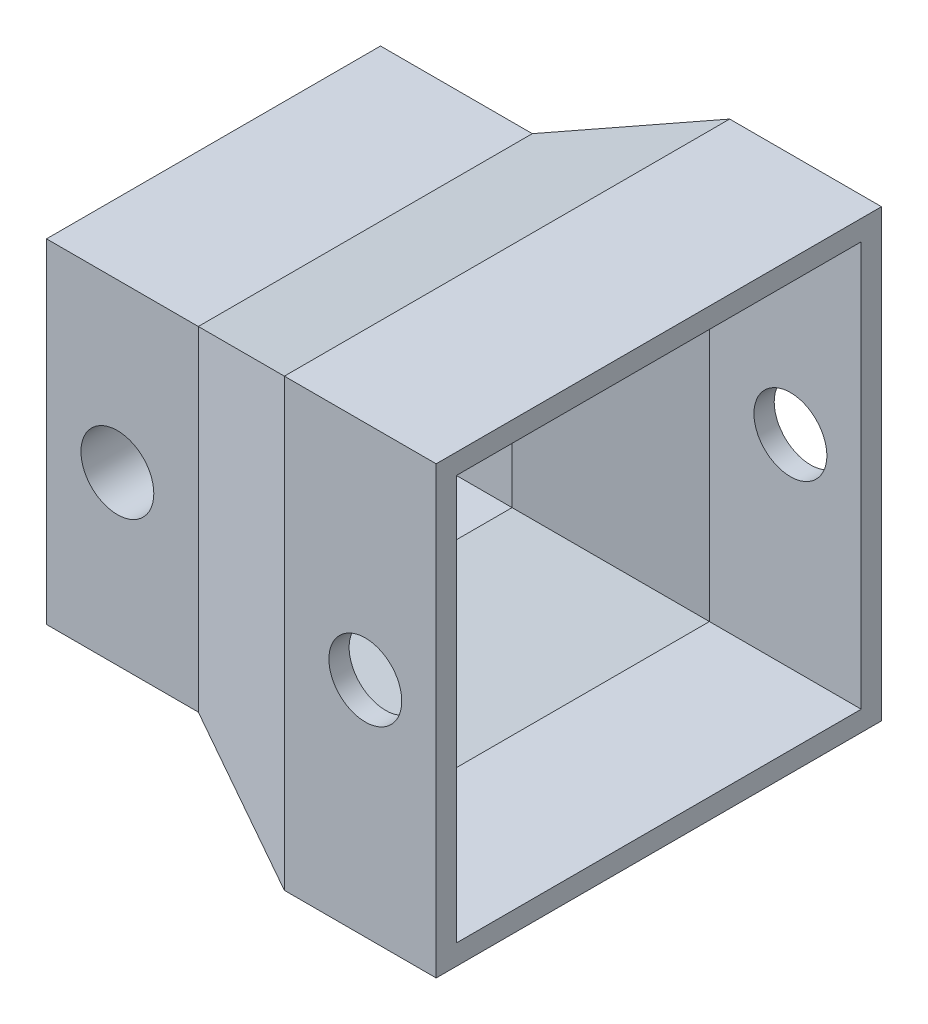
SolidWorks part; units mm, degrees
ref_plane "正面" through (0, 0, 0) normal (0, 0, 1) x (1, 0, 0)
ref_plane "平面" through (0, 0, 0) normal (0, 1, 0) x (1, 0, 0)
ref_plane "右側面" through (0, 0, 0) normal (1, 0, 0) x (0, 0, -1)
sketch "ｽｹｯﾁ1" plane through (0, 0, 0) normal (0, 0, 1) x (1, 0, 0)
  circle A0 centre (0, 0) radius 2.5
  dimension "D1" = 5
extrude "ﾎﾞｽ - 押し出し1" add sketch "ｽｹｯﾁ1" along normal blind 1.5
sketch "ｽｹｯﾁ2" plane through (0, 0, 1.5) normal (0, 0, 1) x (1, 0, 0)
  circle A0 centre (0, 0) radius 3.5
  dimension "D1" = 7
extrude "ﾎﾞｽ - 押し出し2" add sketch "ｽｹｯﾁ2" along normal blind 1
sketch "ｽｹｯﾁ3" plane through (0, 0, 2.5) normal (0, 0, 1) x (1, 0, 0)
  circle A0 centre (0, 0) radius 2.5 construction
  circle A1 centre (0, 0) radius 2.5
extrude "ﾎﾞｽ - 押し出し3" add sketch "ｽｹｯﾁ3" along normal blind 2.5
sketch "ｽｹｯﾁ4" plane through (0, 0, 5) normal (0, 0, 1) x (1, 0, 0)
  circle A1 centre (0, 0) radius 3.5
  circle A2 centre (0, 0) radius 3.5
  dimension "D1" = 0
extrude "ﾎﾞｽ - 押し出し4" add sketch "ｽｹｯﾁ4" along normal blind 1
sketch "ｽｹｯﾁ5" plane through (0, 0, 6) normal (0, 0, 1) x (1, 0, 0)
  circle A0 centre (0, 0) radius 2.5 construction
  circle A1 centre (0, 0) radius 2.5
extrude "ﾎﾞｽ - 押し出し5" add sketch "ｽｹｯﾁ5" along normal blind 2.5
sketch "ｽｹｯﾁ6" plane through (0, 0, 8.5) normal (0, 0, 1) x (1, 0, 0)
  circle A1 centre (0, 0) radius 3.5
  circle A2 centre (0, 0) radius 3.5
  dimension "D1" = 0
extrude "ﾎﾞｽ - 押し出し6" add sketch "ｽｹｯﾁ6" along normal blind 1
sketch "ｽｹｯﾁ7" plane through (0, 0, 9.5) normal (0, 0, 1) x (1, 0, 0)
  circle A0 centre (0, 0) radius 2.5 construction
  circle A1 centre (0, 0) radius 2.5
extrude "ﾎﾞｽ - 押し出し7" add sketch "ｽｹｯﾁ7" along normal blind 2.5
sketch "ｽｹｯﾁ10" plane through (0, 0, 12) normal (0, 0, 1) x (1, 0, 0)
  circle A1 centre (0, 0) radius 3.5
  circle A2 centre (0, 0) radius 3.5
  dimension "D1" = 0
extrude "ﾎﾞｽ - 押し出し9" add sketch "ｽｹｯﾁ10" along normal blind 1
sketch "ｽｹｯﾁ11" plane through (0, 0, 13) normal (0, 0, 1) x (1, 0, 0)
  circle A0 centre (0, 0) radius 2.5 construction
  circle A1 centre (0, 0) radius 2.5
extrude "ﾎﾞｽ - 押し出し10" add sketch "ｽｹｯﾁ11" along normal blind 1.5
sketch "ｽｹｯﾁ12" plane through (0, 0, 14.5) normal (0, 0, 1) x (1, 0, 0)
  circle A0 centre (0, 0) radius 1.8
  dimension "D1" = 3.6
extrude "ｶｯﾄ - 押し出し2" cut sketch "ｽｹｯﾁ12" against normal through all
ref_plane "平面1" through (15, 0, 0) normal (1, 0, 0) x (0, 0, -1)
sketch "ｽｹｯﾁ13" plane through (15, 0, 0) normal (1, 0, 0) x (0, 0, -1)
  line L0 (0, 0) -> (-7.25, 0) construction
  line L1 (-18.25, -11) -> (3.75, -11)
  line L2 (-18.25, -11) -> (-18.25, 11)
  line L3 (-18.25, 11) -> (3.75, 11)
  line L4 (3.75, -11) -> (3.75, 11)
  line L5 (-18.25, -11) -> (3.75, 11) construction
  line L6 (-18.25, 11) -> (3.75, -11) construction
  line L7 (-7.25, 0) -> (-14.5, 0) construction
  line L8 (-14.5, 2.5) -> (-14.5, -2.5) construction
  line L10 (2.75, -10) -> (-17.25, -10)
  line L11 (2.75, -10) -> (2.75, 10)
  line L12 (2.75, 10) -> (-17.25, 10)
  line L13 (-17.25, -10) -> (-17.25, 10)
  line L14 (2.75, -10) -> (-17.25, 10) construction
  line L15 (2.75, 10) -> (-17.25, -10) construction
  point P4 (-7.25, 0)
  dimension "D1" = 22
  dimension "D2" = 22
  dimension "D3" = 1
extrude "ﾎﾞｽ - 押し出し11" add sketch "ｽｹｯﾁ13" along normal blind 3.5 and the other way blind 4 separate body
sketch "ｽｹｯﾁ14" plane through (0, 0, 0) normal (1, 0, 0) x (0, 0, -1)
  line L0 (-18.25, 11) -> (3.75, -11) construction
  line L1 (1, -8.25) -> (-15.5, -8.25)
  line L2 (1, -8.25) -> (1, 8.25)
  line L3 (1, 8.25) -> (-15.5, 8.25)
  line L4 (-15.5, -8.25) -> (-15.5, 8.25)
  line L5 (1, -8.25) -> (-15.5, 8.25) construction
  line L6 (1, 8.25) -> (-15.5, -8.25) construction
  line L7 (-14.5, 2.5) -> (-14.5, -2.5) construction
  line L8 (0, -7.25) -> (-14.5, -7.25)
  line L9 (0, -7.25) -> (0, 7.25)
  line L10 (0, 7.25) -> (-14.5, 7.25)
  line L11 (-14.5, -7.25) -> (-14.5, 7.25)
  line L12 (0, -7.25) -> (-14.5, 7.25) construction
  line L13 (0, 7.25) -> (-14.5, -7.25) construction
  point P0 (-7.25, 0)
  point P9 (-7.25, 0)
  dimension "D1" = 1
extrude "ﾎﾞｽ - 押し出し12" add sketch "ｽｹｯﾁ14" along normal blind 4 and the other way blind 3.5
sketch "ｽｹｯﾁ16" plane through (11, 0, 0) normal (-1, 0, 0) x (0, 0, 1)
  line L0 (-3.75, 11) -> (-2.75, 10)
  line L1 (-2.75, 10) -> (17.25, 10)
  line L2 (17.25, 10) -> (18.25, 11)
  line L3 (18.25, 11) -> (-3.75, 11)
sketch "ｽｹｯﾁ17" plane through (4, 0, 0) normal (1, 0, 0) x (0, 0, -1)
  line L0 (-15.5, 8.25) -> (-14.5, 7.25)
  line L1 (-14.5, 7.25) -> (0, 7.25)
  line L2 (0, 7.25) -> (1, 8.25)
  line L3 (1, 8.25) -> (-15.5, 8.25)
loft "ﾛﾌﾄ2" add profiles "ｽｹｯﾁ16", "ｽｹｯﾁ17" connector at (11, 10, -2.75) connector at (4, 7.25, 0)
sketch "ｽｹｯﾁ18" plane through (0, 0, 0) normal (0, 1, 0) x (1, 0, 0)
  line L0 (0.25, 1) -> (0.25, -15.5)
  line L1 (-3.5, 1) -> (4, 1) construction
  line L2 (-3.5, -15.5) -> (4, -15.5) construction
  line L3 (0.25, -7.25) -> (-9.75, -7.25)
  dimension "D1" = 10
pattern_circular "円形ﾊﾟﾀｰﾝ1" count 4 over 360 about axis through (0.25, 0, 7.25) along (-1, 0, 0) of "ﾛﾌﾄ2" reverse direction yes
sketch "ｽｹｯﾁ19" plane through (0, 0, 15.5) normal (0, 0, 1) x (1, 0, 0)
  circle A1 centre (0, 0) radius 1.8
  circle A2 centre (0, 0) radius 1.8
  dimension "D1" = 0
extrude "ｶｯﾄ - 押し出し3" cut sketch "ｽｹｯﾁ19" against normal through all
sketch "ｽｹｯﾁ20" plane through (0, 0, 18.25) normal (0, 0, 1) x (1, 0, 0)
  line L0 (15, -3.85) -> (15, 3.85) construction
  line L1 (0, 0) -> (15, 0) construction
  circle A0 centre (15, 0) radius 1.8
  dimension "D1" = 3.6
extrude "ｶｯﾄ - 押し出し4" cut sketch "ｽｹｯﾁ20" against normal through all
